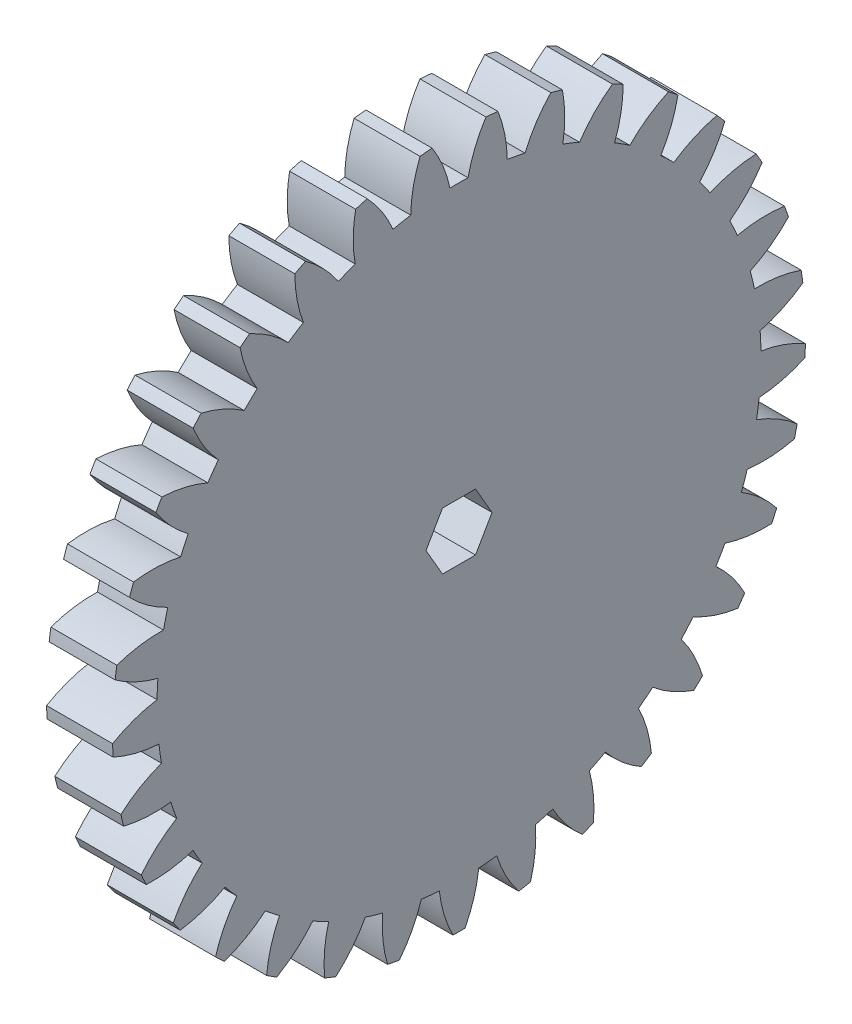
SolidWorks part; units mm, degrees
ref_plane "Plane1" through (0, 0, 0) normal (0, 0, 1) x (1, 0, 0)
ref_plane "Plane2" through (0, 0, 0) normal (0, 1, 0) x (1, 0, 0)
ref_plane "Plane3" through (0, 0, 0) normal (1, 0, 0) x (0, 0, -1)
sketch "HoldingSke" plane through (0, 0, 0) normal (0, 1, 0) x (1, 0, 0)
  line L0 (0, 0) -> (0.5591, -0.3631)
  line L1 (-15, 0) -> (100, 0) construction
  line L2 (0, 0) -> (-2.1039, 2.3779)
  line L3 (0, 0) -> (-11.863, 4.5341)
  line L4 (0, 0) -> (7.2428, 4.7035)
  line L5 (0, 0) -> (-46.8476, -17.4728)
  line L6 (0, 0) -> (-4.1448, -2.7965)
  line L7 (-2.1039, 2.3779) -> (8.6586, 51.2059)
  line L8 (-76.2, 54.61) -> (-75.3, 54.61)
  line L9 (-71.009, 38.7566) -> (-53.1078, 45.2721)
  line L10 (-76.2, 71.12) -> (104.1128, 71.12)
  line L11 (0, 0) -> (-5, 0)
  line L12 (-76.2, 101.6) -> (-76.147, 101.6)
  line L13 (24.9733, 27.94) -> (52.9518, 28.4284)
  line L14 (24.9733, 27.94) -> (24.9743, 27.94)
  line L15 (24.9733, 27.94) -> (100.4006, 29.5858)
  line L16 (-63.627, -1.5) -> (-12.827, -1.5)
  circle A0 centre (0, 0) radius 2.5
  circle A1 centre (0, 0) radius 22.874
  circle A2 centre (0, 0) radius 37.5
  circle A3 centre (0, 0) radius 2.5
  dimension "MHD" = 45.748
  dimension "Hub_dia" = 75
  dimension "Bore" = 5
  dimension "MBD" = 5
  dimension "Num_teeth" = 33
  dimension "Pitch" = 0.6667
  dimension "Overall_len" = 50
  dimension "Show_teeth" = 33
  dimension "Thickness" = 5
  dimension "OAL" = 50.0001
  dimension "T_dim" = 0.9
  dimension "Ap" = 20
  dimension "H" = 19.05
  dimension "Pitch_radius" = 180.3128
  dimension "Width" = 5
  dimension "Backlash" = 0.053
  dimension "Addendum_fac" = 1
  dimension "Dedendum_fac" = 1.25
  dimension "Clearance_fac" = 0.25
  dimension "Dedendum_add" = 0.001
  dimension "Module" = 1.5
sketch "BasProSke" plane through (0, 0, 0) normal (0, 1, 0) x (1, 0, 0)
  line L0 (-10, 0) -> (60, 0) construction
  line L1 (0, 0) -> (0, 26.25)
  line L2 (0, 0) -> (5, 0)
  line L3 (5, 0) -> (5, 26.25)
  line L4 (5, 26.25) -> (0, 26.25)
  dimension "Thickness" = 5
  dimension "Diameter" = 52.5
revolve "Base-Revolve" add sketch "BasProSke" angle 360 about L0
sketch "TooCutSke" plane through (0, 0, 0) normal (1, 0, 0) x (0, 0, -1)
  line L1 (0, 0) -> (0, 107) construction
  line L2 (0, 0) -> (-1.2704, 24.7174) construction
  line L3 (0, 0) -> (-4.7008, 49.2285) construction
  line L4 (-1.2704, 24.7174) -> (-2.3504, 24.6142) construction
  arc A0 (0.6837, 22.8638) -> (-0.6837, 22.8638) centre (0, 0) ccw
  arc A1 (2.0575, 26.1947) -> (-2.0575, 26.1947) centre (0, 0) ccw
  circle A2 centre (0, 0) radius 24.75 construction
  circle A3 centre (0, 0) radius 23.2574 construction
  arc A4 (-0.6837, 22.8638) -> (-2.0575, 26.1947) centre (-10.3699, 20.8176) ccw
  arc A5 (2.0575, 26.1947) -> (0.6837, 22.8638) centre (10.3699, 20.8176) ccw
  dimension "Root_dia" = 45.748
  dimension "Overcut_dia" = 52.5508
  dimension "Pitch_dia" = 49.5
  dimension "Base_dia" = 46.5148
  dimension "Flank_rad" = 9.9
  dimension "Half_ang" = 5.455
  dimension "Half_CT" = 1.0849
extrude "ToothCut" cut sketch "TooCutSke" along normal through all
fillet "Breaks" [suppressed] radius 0.03 tangent propagation no
fillet "RootFillets" [suppressed] radius 0.376
pattern_circular "TeethCuts" count 33 every 10.909 about axis through (-10, 0, 0) along (1, 0, 0) of "ToothCut", "RootFillets", "Breaks"
sketch "HubNeaOneSke" plane through (0, 0, 0) normal (-1, 0, 0) x (0, 0, 1)
  circle A0 centre (0, 0) radius 22.874
  dimension "Diameter" = 45.748
extrude "HubNearOne" [suppressed] add sketch "HubNeaOneSke" along normal blind 45.0001
sketch "HubNeaBotSke" plane through (0, 0, 0) normal (-1, 0, 0) x (0, 0, 1)
  circle A0 centre (0, 0) radius 22.874
  dimension "Diameter" = 45.748
extrude "HubNearBoth" [suppressed] add sketch "HubNeaBotSke" along normal blind 22.5
ref_plane "FarPln" through (5, 0, 0) normal (1, 0, 0) x (0, 0, -1)
sketch "HubFarSke" plane through (5, 0, 0) normal (1, 0, 0) x (0, 0, -1)
  circle A0 centre (0, 0) radius 22.874
  dimension "Diameter" = 45.748
extrude "HubFar" [suppressed] add sketch "HubFarSke" along normal blind 22.5
sketch "BorSke" plane through (0, 0, 0) normal (1, 0, 0) x (0, 0, -1)
  line L1 (-2.5, 0) -> (-1.25, -2.1651)
  line L2 (-1.25, -2.1651) -> (1.25, -2.1651)
  line L3 (1.25, -2.1651) -> (2.5, 0)
  line L4 (2.5, 0) -> (1.25, 2.1651)
  line L5 (1.25, 2.1651) -> (-1.25, 2.1651)
  line L6 (-1.25, 2.1651) -> (-2.5, 0)
  circle A0 centre (0, 0) radius 2.5 construction
  circle A1 centre (0, 0) radius 2.1651 construction
  point P2 (-2.5, 0)
  dimension "Diameter" = 5
extrude "Bore" cut sketch "BorSke" along normal mid plane 100.0001
sketch "KeySke" plane through (0, 0, 0) normal (1, 0, 0) x (0, 0, -1)
  line L0 (-1, 0) -> (-1, 3.4)
  line L1 (-1, 3.4) -> (1, 3.4)
  line L2 (1, 3.4) -> (1, 0)
  line L3 (0, 0) -> (0, 34) construction
  line L4 (-1, 0) -> (1, 0)
  dimension "Offset" = 3.4
  dimension "Width" = 2
extrude "Keyway" [suppressed] cut sketch "KeySke" along normal mid plane 100.0001
pattern_circular "Keyway2" [suppressed] count 2 every 90 about axis through (-10, 0, 0) along (1, 0, 0) reverse direction yes
sketch "Sketch1" plane through (0, 0, 0) normal (-1, 0, 0) x (0, 0, 1)
  line L0 (-1.25, -2.1651) -> (1.25, -2.1651) construction
  line L1 (-2.5, 0) -> (-1.25, -2.1651) construction
  line L2 (-1.25, 2.1651) -> (-2.5, 0) construction
  line L3 (1.25, 2.1651) -> (-1.25, 2.1651) construction
  line L4 (2.5, 0) -> (1.25, 2.1651) construction
  line L5 (1.25, -2.1651) -> (2.5, 0) construction
  line L6 (2.5, 0) -> (1.25, 2.1651)
  line L7 (1.25, 2.1651) -> (-1.25, 2.1651)
  line L8 (-1.25, 2.1651) -> (-2.5, 0)
  line L9 (-2.5, 0) -> (-1.25, -2.1651)
  line L10 (-1.25, -2.1651) -> (1.25, -2.1651)
  line L11 (1.25, -2.1651) -> (2.5, 0)
  arc A80 (0.1868, -8.9981) -> (0.8757, -5.5554) centre (-1.8542, -6.7994) ccw
  arc A81 (-0.1868, -8.9981) -> (0.1868, -8.9981) centre (0, 0) ccw
  arc A82 (-0.8757, -5.5554) -> (-0.1868, -8.9981) centre (1.8542, -6.7994) ccw
  arc A83 (-2.5569, -5.0091) -> (-0.8757, -5.5554) centre (0, 0) ccw
  arc A84 (-5.1378, -7.3894) -> (-2.5569, -5.0091) centre (-5.4967, -4.4109) ccw
  arc A85 (-5.4401, -7.1698) -> (-5.1378, -7.3894) centre (0, 0) ccw
  arc A86 (-3.9738, -3.9797) -> (-5.4401, -7.1698) centre (-2.4965, -6.5907) ccw
  arc A87 (-5.0129, -2.5496) -> (-3.9738, -3.9797) centre (0, 0) ccw
  arc A88 (-8.4999, -2.9582) -> (-5.0129, -2.5496) centre (-7.0396, -0.3377) ccw
  arc A89 (-8.6154, -2.6029) -> (-8.4999, -2.9582) centre (0, 0) ccw
  arc A90 (-5.5541, -0.8839) -> (-8.6154, -2.6029) centre (-5.8936, -3.8646) ccw
  arc A91 (-5.5541, 0.8839) -> (-5.5541, -0.8839) centre (0, 0) ccw
  arc A92 (-8.6154, 2.6029) -> (-5.5541, 0.8839) centre (-5.8936, 3.8646) ccw
  arc A93 (-8.4999, 2.9582) -> (-8.6154, 2.6029) centre (0, 0) ccw
  arc A94 (-5.0129, 2.5496) -> (-8.4999, 2.9582) centre (-7.0396, 0.3377) ccw
  arc A95 (-3.9738, 3.9797) -> (-5.0129, 2.5496) centre (0, 0) ccw
  arc A96 (-5.4401, 7.1698) -> (-3.9738, 3.9797) centre (-2.4965, 6.5907) ccw
  arc A97 (-5.1378, 7.3894) -> (-5.4401, 7.1698) centre (0, 0) ccw
  arc A98 (-2.5569, 5.0091) -> (-5.1378, 7.3894) centre (-5.4967, 4.4109) ccw
  arc A99 (-0.8757, 5.5554) -> (-2.5569, 5.0091) centre (0, 0) ccw
  arc A100 (-0.1868, 8.9981) -> (-0.8757, 5.5554) centre (1.8542, 6.7994) ccw
  arc A101 (0.1868, 8.9981) -> (-0.1868, 8.9981) centre (0, 0) ccw
  arc A102 (0.8757, 5.5554) -> (0.1868, 8.9981) centre (-1.8542, 6.7994) ccw
  arc A103 (2.5569, 5.0091) -> (0.8757, 5.5554) centre (0, 0) ccw
  arc A104 (5.1378, 7.3894) -> (2.5569, 5.0091) centre (5.4967, 4.4109) ccw
  arc A105 (5.4401, 7.1698) -> (5.1378, 7.3894) centre (0, 0) ccw
  arc A106 (3.9738, 3.9797) -> (5.4401, 7.1698) centre (2.4965, 6.5907) ccw
  arc A107 (5.0129, 2.5496) -> (3.9738, 3.9797) centre (0, 0) ccw
  arc A108 (8.4999, 2.9582) -> (5.0129, 2.5496) centre (7.0396, 0.3377) ccw
  arc A109 (8.6154, 2.6029) -> (8.4999, 2.9582) centre (0, 0) ccw
  arc A110 (5.5541, 0.8839) -> (8.6154, 2.6029) centre (5.8936, 3.8646) ccw
  arc A111 (5.5541, -0.8839) -> (5.5541, 0.8839) centre (0, 0) ccw
  arc A112 (8.6154, -2.6029) -> (5.5541, -0.8839) centre (5.8936, -3.8646) ccw
  arc A113 (8.4999, -2.9582) -> (8.6154, -2.6029) centre (0, 0) ccw
  arc A114 (5.0129, -2.5496) -> (8.4999, -2.9582) centre (7.0396, -0.3377) ccw
  arc A115 (3.9738, -3.9797) -> (5.0129, -2.5496) centre (0, 0) ccw
  arc A116 (5.4401, -7.1698) -> (3.9738, -3.9797) centre (2.4965, -6.5907) ccw
  arc A117 (5.1378, -7.3894) -> (5.4401, -7.1698) centre (0, 0) ccw
  arc A118 (2.5569, -5.0091) -> (5.1378, -7.3894) centre (5.4967, -4.4109) ccw
  arc A119 (0.8757, -5.5554) -> (2.5569, -5.0091) centre (0, 0) ccw
extrude "Boss-Extrude1" add sketch "Sketch1" along normal blind 6
equation "' \"Module@HoldingSke\" = 6.35"
equation "' \"Num_teeth@HoldingSke\" = 12"
equation "' \"Ap@HoldingSke\" =  20"
equation "' \"Ap@HoldingSke\" = 20"
equation "' \"Width@HoldingSke\" = 0.5 * 25.4"
equation "' \"Hub_dia@HoldingSke\"= 1 * 25.4"
equation "' \"Hub_dia@HoldingSke\" = 1 * 25.4"
equation "' \"Overall_len@HoldingSke\" = 1.0 * 25.4"
equation "' \"Bore@HoldingSke\" = 0.75 * 25.4"
equation "' \"T_dim@HoldingSke\" = 0.1 * 25.4"
equation "' \"Width@KeySke\" = 0.25 * 25.4"
equation "' \"Show_teeth@HoldingSke\" = 13"
equation "' \"Backlash@HoldingSke\" = 0.009 * 25.4"
equation "' \"Addendum_fac@HoldingSke\" = 1.0"
equation "' \"Dedendum_fac@HoldingSke\" = 1.25"
equation "' \"Dedendum_add@HoldingSke\" = 0.00005 * 25.4"
equation "' \"Clearance_fac@HoldingSke\" = 0.25"
equation "\"Pitch@HoldingSke\" = 1 / \"Module@HoldingSke\""
equation "\"Overcut_dia@TooCutSke\" = (\"Num_teeth@HoldingSke\" + 2 * \"Addendum_fac@HoldingSke\") / \"Pitch@HoldingSke\" + 0.002 * 25.4"
equation "\"Pitch_dia@TooCutSke\" = \"Num_teeth@HoldingSke\" / \"Pitch@HoldingSke\""
equation "\"Base_dia@TooCutSke\" = \"Num_teeth@HoldingSke\" / \"Pitch@HoldingSke\" * cos((\"Ap@HoldingSke\"  * 3.14159265 / 180))"
equation "\"Root_dia@TooCutSke\" = (\"Num_teeth@HoldingSke\" + 2) / \"Pitch@HoldingSke\" - 2 * (\"Addendum_fac@HoldingSke\" + \"Dedendum_fac@HoldingSke\") / \"Pitch@HoldingSke\" - \"Dedendum_add@HoldingSke\" * 2"
equation "\"Half_ang@TooCutSke\" = 180 / \"Num_teeth@HoldingSke\""
equation "\"Half_CT@TooCutSke\" = \"Num_teeth@HoldingSke\" / \"Pitch@HoldingSke\" * sin((3.14159265 / 2 / \"Num_teeth@HoldingSke\")) / 2 - 7 * \"Backlash@HoldingSke\" / 4"
equation "\"Flank_rad@TooCutSke\" = \"Num_teeth@HoldingSke\" / \"Pitch@HoldingSke\" / 5"
equation "\"Radius@RootFillets\" = \"Clearance_fac@HoldingSke\" / \"Pitch@HoldingSke\" + \"Dedendum_add@HoldingSke\""
equation "\"Break_rad@Breaks\" = 0.02 / \"Pitch@HoldingSke\""
equation "\"Thickness@HoldingSke\" = \"Width@HoldingSke\""
equation "\"OAL@HoldingSke\" = \"Thickness@HoldingSke\""
equation "\"MHD@HoldingSke\" = (\"Num_teeth@HoldingSke\" + 2) / \"Pitch@HoldingSke\" - 2 * (\"Addendum_fac@HoldingSke\" + \"Dedendum_fac@HoldingSke\")  / \"Pitch@HoldingSke\" - \"Dedendum_add@HoldingSke\" * 2"
equation "\"MBD@HoldingSke\" = (\"Num_teeth@HoldingSke\" + 2) / \"Pitch@HoldingSke\" - 2 * (\"Addendum_fac@HoldingSke\" + \"Dedendum_fac@HoldingSke\")  / \"Pitch@HoldingSke\" - \"Dedendum_add@HoldingSke\" * 2 - 0.002 * 25.4"
equation "\"MHD@HoldingSke\" = ((sgn( \"MHD@HoldingSke\" - \"Hub_dia@HoldingSke\" )-1)*( \"MHD@HoldingSke\" - \"Hub_dia@HoldingSke\" ))/-2+ \"Hub_dia@HoldingSke\""
equation "\"MBD@HoldingSke\" = ((sgn( \"MBD@HoldingSke\" - \"Bore@HoldingSke\" )-1)*( \"MBD@HoldingSke\" - \"Bore@HoldingSke\" ))/-2+ \"Bore@HoldingSke\""
equation "\"OAL@HoldingSke\" = ((sgn( \"OAL@HoldingSke\" - \"Overall_len@HoldingSke\" )+1)*( \"OAL@HoldingSke\" - \"Overall_len@HoldingSke\" ))/2 + \"Overall_len@HoldingSke\" + 0.000002 * 25.4"
equation "\"Num_teeth@TeethCuts\" = int( \"Show_teeth@HoldingSke\" ) + 1"
equation "\"Num_teeth@TeethCuts\" = ((sgn( \"Num_teeth@TeethCuts\" - \"Num_teeth@HoldingSke\" )-1)*( \"Num_teeth@TeethCuts\" - \"Num_teeth@HoldingSke\" ))/-2+ \"Num_teeth@HoldingSke\""
equation "\"Num_teeth@TeethCuts\" = ((sgn( \"Num_teeth@TeethCuts\" - 2.0)+1)*( \"Num_teeth@TeethCuts\" - 2.0))/2 +2.0"
equation "\"Angle@TeethCuts\" = 360.0 / \"Num_teeth@HoldingSke\""
equation "\"Diameter@BasProSke\" = (\"Num_teeth@HoldingSke\" + 2 * \"Addendum_fac@HoldingSke\") / \"Pitch@HoldingSke\""
equation "\"Thickness@BasProSke\"  = \"Thickness@HoldingSke\""
equation "' \"Fillet_rad@BasProSke\" =  \"Thickness@HoldingSke\" * 0.05"
equation "' \"Fillet_rad@BasProSke\" = \"Thickness@HoldingSke\" * 0.05"
equation "\"MHD@HoldingSke\" = ((sgn( \"MHD@HoldingSke\" - \"Root_dia@TooCutSke\" )-1)*( \"MHD@HoldingSke\" - \"Root_dia@TooCutSke\" ))/-2+ \"Root_dia@TooCutSke\""
equation "\"Diameter@HubNeaOneSke\" = \"MHD@HoldingSke\""
equation "\"Length@HubNearOne\" = \"OAL@HoldingSke\" - \"Thickness@BasProSke\""
equation "\"Diameter@HubNeaBotSke\" = \"MHD@HoldingSke\""
equation "\"Length@HubNearBoth\" = ( \"OAL@HoldingSke\" - \"Thickness@BasProSke\" ) / 2.0"
equation "\"Thickness@FarPln\" = \"Thickness@BasProSke\""
equation "\"Diameter@HubFarSke\" = \"MHD@HoldingSke\""
equation "\"Length@HubFar\" = ( \"OAL@HoldingSke\" - \"Thickness@BasProSke\" ) / 2.0"
equation "\"Diameter@BorSke\" = \"MBD@HoldingSke\""
equation "\"D1@Bore\" = \"OAL@HoldingSke\" * 2.0"
equation "\"D1@Keyway\" = \"OAL@HoldingSke\" * 2.0"
equation "\"Offset@KeySke\" = \"T_dim@HoldingSke\" + \"MBD@HoldingSke\" / 2.0"
